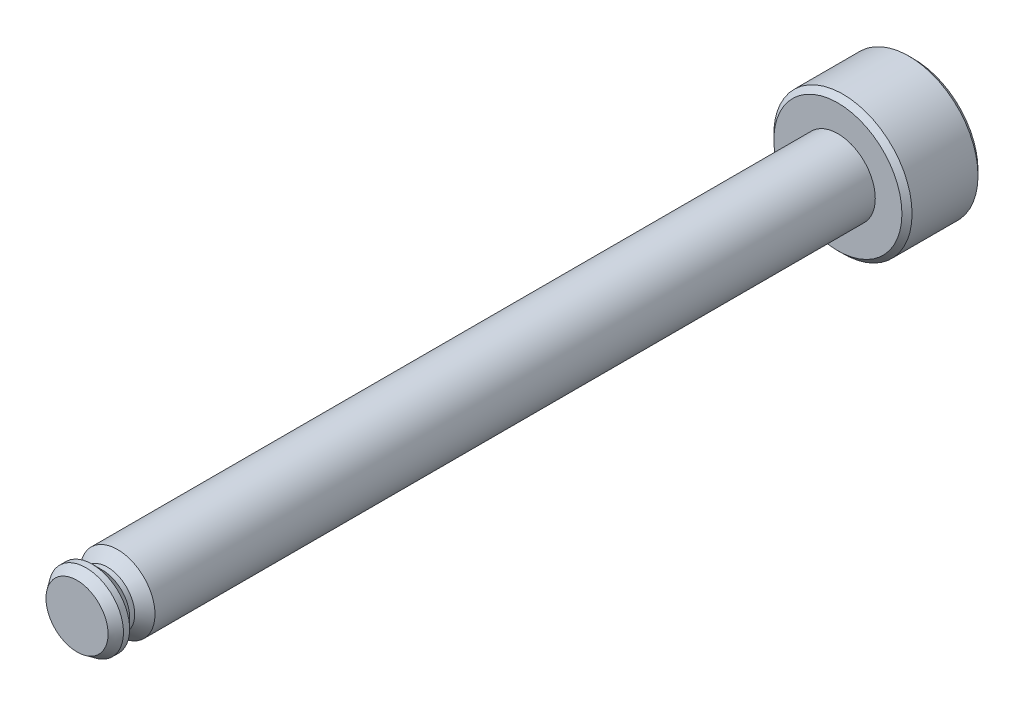
SolidWorks part; units mm, degrees
ref_plane "Front" through (0, 0, 0) normal (0, 0, 1) x (1, 0, 0)
ref_plane "Top" through (0, 0, 0) normal (0, 1, 0) x (1, 0, 0)
ref_plane "Right" through (0, 0, 0) normal (1, 0, 0) x (0, 0, -1)
sketch "Sketch2" plane through (0, 0, 0) normal (0, 0, 1) x (1, 0, 0)
  circle A0 centre (0, 0) radius 1.475
  dimension "D1" = 2.95
extrude "Shaft" add sketch "Sketch2" along normal blind 30
sketch "Sketch5" plane through (0, 0, 0) normal (0, 0, 1) x (1, 0, 0)
  circle A0 centre (0, 0) radius 2.725
  dimension "D1" = 5.45
extrude "Head" add sketch "Sketch5" against normal blind 3
sketch "Sketch4" plane through (0, 0, 0) normal (1, 0, 0) x (0, 0, -1)
  line L0 (0, 0) -> (-54.4, 0) construction
  line L1 (-54.4, 0) -> (-54.4, 4.3666) construction
  line L2 (-54.9, 1.475) -> (-53.9, 1.475)
  line L3 (0, 1.475) -> (-30, 1.475) construction
  line L6 (-53.9, 1.475) -> (-54.3, 1.075)
  line L7 (-54.3, 1.075) -> (-54.5, 1.075)
  line L8 (-54.5, 1.075) -> (-54.9, 1.475)
  line L10 (-54.4, 37.6935) -> (-54.4, -62.3065) construction
  dimension "D2" = 1
  dimension "D3" = 45
  dimension "D4" = 0.4
revolve "e-Clip Notch Short" [suppressed] cut sketch "Sketch4" angle 360 about L0
chamfer "Chamfer1" distance 0.25 angle 55 1 edges at (1.475, 0, 30) first distance on face at (1.475, 0, 30)
chamfer "Deburs" distance 0.2 angle 45 2 edges at (2.725, 0, 0) (2.725, 0, -3)
sketch "Sketch6" plane through (0, 0, 0) normal (1, 0, 0) x (0, 0, -1)
  line L0 (0, 0) -> (-28.9, 0) construction
  line L1 (-28.9, 0) -> (-28.9, 1.075) construction
  line L2 (0, 1.475) -> (-29.643, 1.475) construction
  line L3 (-29.4, 1.475) -> (-28.4, 1.475)
  line L4 (-28.4, 1.475) -> (-28.8, 1.075)
  line L5 (-28.8, 1.075) -> (-29, 1.075)
  line L6 (-29, 1.075) -> (-29.4, 1.475)
  line L7 (-28.9, 1.075) -> (-28.9, 1.475) construction
  line L8 (-54.9, 1.475) -> (-53.9, 1.475) construction
  line L9 (-54.5, 1.075) -> (-54.9, 1.475) construction
  line L10 (-28.9, 50) -> (-28.9, -50) construction
revolve "e-Clip Notch Long" cut sketch "Sketch6" angle 360 about L0
equation "\"D1@Sketch2\"=\"Plastic Hardware OD@Box Assy.Assembly\""
equation "\"D1@Sketch5\"=\"Hardware Head Countersink Diameter@Box Assy.Assembly\"-.3mm"
equation "\"D1@Head\"=\"Countersink Depth@Box Assy.Assembly\""
